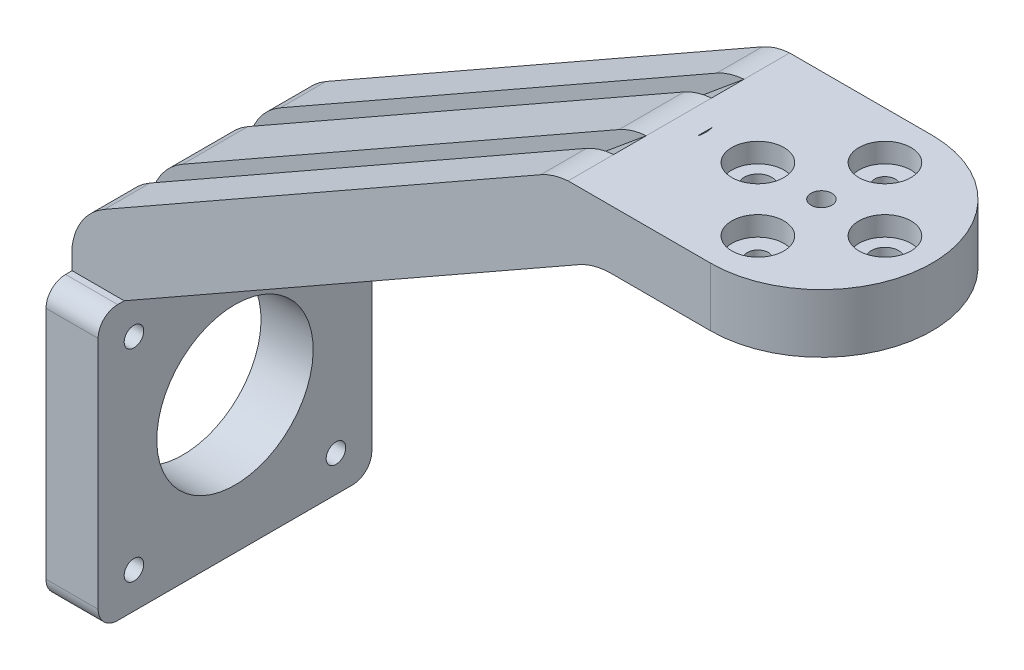
SolidWorks part; units mm, degrees
ref_plane "前视基准面" through (0, 0, 0) normal (0, 0, 1) x (1, 0, 0)
ref_plane "上视基准面" through (0, 0, 0) normal (0, 1, 0) x (1, 0, 0)
ref_plane "右视基准面" through (0, 0, 0) normal (1, 0, 0) x (0, 0, -1)
other "Configuration Table"
sketch "草图1" plane through (0, 0, 0) normal (0, 1, 0) x (1, 0, 0)
  line L0 (0, 0) -> (90, 0) construction
  line L1 (0, 17) -> (90, 17)
  line L2 (0, -17) -> (90, -17)
  line L3 (45, 0) -> (45, -50000) construction
  line L4 (0, 0) -> (50000, 0) construction
  line L5 (90, 0) -> (90, -50000) construction
  arc A0 (0, 17) -> (0, -17) centre (0, 0) ccw
  arc A1 (90, -17) -> (90, 17) centre (90, 0) ccw
  circle A3 centre (90, 0) radius 9.75 construction
  circle A5 centre (90, 0) radius 1.6
  circle A13 centre (90, 0) radius 1.6
  circle A15 centre (90, 9.75) radius 1.6
  circle A16 centre (99.75, 0) radius 2.1
  circle A17 centre (90, -9.75) radius 1.6
  circle A18 centre (80.25, 0) radius 2.1
  point P3 (45, 0)
  dimension "D3" = 19.5
  dimension "D4" = 3.2
  dimension "D5" = 4.2
  dimension "D6" = 3.2
  dimension "D1" = 34
  dimension "D2" = 90
extrude "凸台-拉伸2" add sketch "草图1" along normal blind 9
sketch "草图3" plane through (0, 9, 0) normal (0, 1, 0) x (1, 0, 0)
  line L0 (45, -17) -> (45, -50017) construction
  line L1 (0, -17) -> (90, -17) construction
  circle A14 centre (90, 0) radius 9.75 construction
  circle A15 centre (90, 9.75) radius 4
  circle A19 centre (99.75, 0) radius 4
  circle A20 centre (90, -9.75) radius 4
  circle A21 centre (80.25, 0) radius 4
  point P4 (90, 0)
  point P16 (80, -10)
  point P17 (90, 0)
  point P20 (45, -17)
  dimension "D1" = 8
extrude "切除-拉伸2" cut sketch "草图3" against normal blind 3
sketch "草图4" plane through (0, 9, 0) normal (0, 1, 0) x (1, 0, 0)
  line L1 (0, -17) -> (-22.8348, -17)
  line L2 (0, -17) -> (0, 17.0216)
  line L3 (0, 17.0216) -> (-22.8348, 17.0216)
  line L4 (-22.8348, -17) -> (-22.8348, 17.0216)
extrude "切除-拉伸3" cut sketch "草图4" against normal blind 10
sketch "草图5" plane through (0, 9, 0) normal (0, 1, 0) x (1, 0, 0)
  line L1 (0, -17) -> (-8, -17)
  line L2 (0, -17) -> (0, 17)
  line L3 (0, 17) -> (-8, 17)
  line L4 (-8, -17) -> (-8, 17)
  circle A0 centre (-4, 10) radius 1.6
  circle A1 centre (-4, 0) radius 1.6
  circle A2 centre (-4, -10) radius 1.6
  dimension "D3" = 3.2
  dimension "D4" = 7
  dimension "D1" = 34
  dimension "D2" = 8
  dimension "D5" = 4
  dimension "D6" = 3
extrude "凸台-拉伸3" add sketch "草图5" against normal blind 6
sketch "草图6" plane through (0, 9, 0) normal (0, 1, 0) x (1, 0, 0)
  circle A0 centre (-4, 10) radius 3.5
  circle A1 centre (-4, 0) radius 3.5
  circle A2 centre (-4, -10) radius 3.5
  dimension "D2" = 7
  dimension "D1" = 3
extrude "切除-拉伸4" cut sketch "草图6" against normal blind 3
sketch "草图7" plane through (0, 9, 0) normal (0, 1, 0) x (1, 0, 0)
  line L0 (68.25, 0) -> (7, 0) construction
  line L1 (68.25, -4) -> (7, -4)
  line L2 (68.25, 4) -> (7, 4)
  line L3 (-8, 17) -> (-8, -17) construction
  arc A0 (68.25, -4) -> (68.25, 4) centre (68.25, 0) ccw
  arc A1 (7, 4) -> (7, -4) centre (7, 0) ccw
  circle A2 centre (80.25, 0) radius 4 construction
  point P3 (37.625, 0)
  dimension "D2" = 12
  dimension "D3" = 15
  dimension "D1" = 8
extrude "切除-拉伸5" cut sketch "草图7" against normal blind 13
sketch "草图8" plane through (0, 0, 17) normal (0, 0, 1) x (1, 0, 0)
  line L0 (0, -41) -> (72.0801, 0)
  line L2 (-8, -37.7935) -> (-8, -41)
  line L5 (0, 0) -> (90, 0) construction
  line L6 (58.443, 0) -> (-8, -37.7935)
  line L8 (-8, -41) -> (-8, -83)
  line L9 (-8, -83) -> (0, -83)
  line L10 (0, -41) -> (0, -83)
  dimension "D2" = 8
  dimension "D3" = 42
extrude "凸台-拉伸4" add sketch "草图8" against normal blind 35
sketch "草图9" plane through (0, 0, 17) normal (0, 0, 1) x (1, 0, 0)
  line L0 (58.443, 0) -> (68.1232, 9)
  line L1 (-8, 9) -> (90, 9) construction
  line L2 (68.1232, 9) -> (-8, 9)
  line L3 (-8, 9) -> (-8, 0)
  line L4 (-8, 0) -> (58.443, 0)
  point P5 (0, 0)
extrude "切除-拉伸6" cut sketch "草图9" against normal blind 40
sketch "草图10" plane through (27.0962, -29.1441, 0) normal (-0.6809, 0.7324, 0) x (0.7324, 0.6809, 0)
  line L1 (56.0195, 17) -> (-62.3743, 17)
  line L2 (56.0195, 17) -> (56.0195, 18)
  line L3 (56.0195, 18) -> (-62.3743, 18)
  line L4 (-62.3743, 17) -> (-62.3743, 18)
extrude "切除-拉伸7" cut sketch "草图10" against normal blind 40
sketch "草图11" plane through (17.6203, -30.9774, 0) normal (0.4944, -0.8692, 0) x (0.8692, 0.4944, 0)
  line L1 (-27.3155, -17) -> (53.1147, -17)
  line L2 (-27.3155, -17) -> (-27.3155, -24.1461)
  line L3 (-27.3155, -24.1461) -> (53.1147, -24.1461)
  line L4 (53.1147, -17) -> (53.1147, -24.1461)
  point P5 (0, 0)
extrude "切除-拉伸8" cut sketch "草图11" against normal blind 40
sketch "草图12" plane through (0, 0, 17) normal (0, 0, 1) x (1, 0, 0)
  line L0 (72.0801, 0) -> (72.0801, 9)
  line L1 (68.1232, 9) -> (90, 9) construction
  line L2 (72.0801, 9) -> (68.1232, 9)
  line L3 (68.1232, 9) -> (54.7806, -2.0832)
  line L4 (58.443, 0) -> (-8, -37.7935) construction
  line L5 (54.7806, -2.0832) -> (58.1143, -7.944)
  line L6 (0, -41) -> (72.0801, 0) construction
  line L7 (58.1143, -7.944) -> (72.0801, 0)
extrude "凸台-拉伸5" add sketch "草图12" against normal blind 34
sketch "草图13" plane through (0, 0, 0) normal (1, 0, 0) x (0, 0, -1)
  line L0 (-17, -62) -> (49983, -62) construction
  line L1 (-17, -41) -> (-17, -83) construction
  line L2 (0, -41) -> (0, -50041) construction
  line L3 (17, -41) -> (-17, -41) construction
  circle A0 centre (-15.5, -46.5) radius 1.5
  circle A1 centre (15.5, -46.5) radius 1.5
  circle A2 centre (15.5, -77.5) radius 1.5
  circle A3 centre (-15.5, -77.5) radius 1.5
  circle A4 centre (0, -62) radius 12
  point P4 (-17, -62)
  point P9 (0, -41)
  dimension "D1" = 15.5
  dimension "D2" = 3
  dimension "D4" = 24
  dimension "D3" = 15.5
sketch "草图14" plane through (-8, 0, 0) normal (-1, 0, 0) x (0, 0, 1)
  line L0 (200017, -62) -> (-249983, -62) construction
  line L1 (-21, -41) -> (21, -41)
  line L2 (-21, -41) -> (-21, -83)
  line L3 (-21, -83) -> (21, -83)
  line L4 (21, -41) -> (21, -83)
  line L5 (-21, -41) -> (21, -83) construction
  line L6 (-21, -83) -> (21, -41) construction
  line L7 (0, 199959) -> (0, -250041) construction
  point P0 (0, -62)
  dimension "D1" = 42
  dimension "D2" = 42
extrude "凸台-拉伸6" add sketch "草图14" against normal blind 8
extrude "切除-拉伸10" cut sketch "草图13" against normal blind 8
sketch "草图15" plane through (14.2866, -25.1166, 0) normal (-0.4944, 0.8692, 0) x (0.8692, 0.4944, 0)
  line L0 (63.6639, 17) -> (63.6639, -17) construction
  line L1 (-25.6397, 17) -> (63.6639, 17)
  line L2 (-25.6397, 17) -> (-25.6397, 10)
  line L3 (-25.6397, 10) -> (63.6639, 10)
  line L4 (63.6639, 17) -> (63.6639, 10)
  line L5 (-25.6397, 17) -> (-25.6397, -17) construction
  line L6 (-25.6397, 5) -> (63.6639, 5)
  line L7 (-25.6397, 5) -> (-25.6397, -5)
  line L8 (-25.6397, -5) -> (63.6639, -5)
  line L9 (63.6639, 5) -> (63.6639, -5)
  line L11 (-25.6397, -17) -> (63.6639, -17)
  line L12 (-25.6397, -17) -> (-25.6397, -10)
  line L13 (-25.6397, -10) -> (63.6639, -10)
  line L14 (63.6639, -17) -> (63.6639, -10)
  dimension "D1" = 5
  dimension "D2" = 5
  dimension "D3" = 7
  dimension "D4" = 7
extrude "凸台-拉伸7" add sketch "草图15" along normal blind 4
fillet "圆角1" radius 10 6 edges at (67.647, 9.8372, -13.5) (67.647, 9.8372, 0) (67.647, 9.8372, 13.5) (-9.9777, -34.3166, -13.5) (-9.9777, -34.3166, 0) (-9.9777, -34.3166, 13.5)
fillet "圆角2" radius 10 1 edges at (72.0801, 0, 9.0766)
fillet "圆角3" radius 3 4 edges at (-4, -83, 21) (-4, -83, -21) (-4, -41, -21) (-4, -41, 21)
